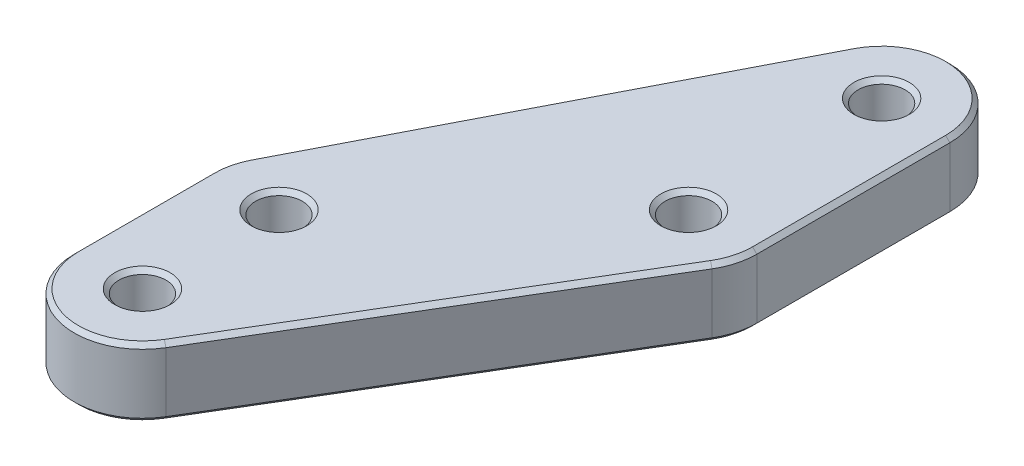
SolidWorks part; units mm, degrees
ref_plane "Front Plane" through (0, 0, 0) normal (0, 0, 1) x (1, 0, 0)
ref_plane "Top Plane" through (0, 0, 0) normal (0, 1, 0) x (1, 0, 0)
ref_plane "Right Plane" through (0, 0, 0) normal (1, 0, 0) x (0, 0, -1)
sketch "Sketch1" plane through (0, 0, 0) normal (0, 1, 0) x (1, 0, 0)
  line L0 (-25.4, -19.05) -> (-25.4, -31.75)
  line L1 (5.4451, -3.267) -> (-13.6049, -35.017)
  line L2 (-24.6959, -16.1437) -> (-5.6459, 20.8641)
  line L3 (6.35, 17.9578) -> (6.35, 0)
  circle A0 centre (0, 0) radius 2.1828
  circle A1 centre (0, 17.9578) radius 2.1828
  circle A2 centre (-19.05, -19.05) radius 2.1828
  circle A3 centre (-19.05, -31.75) radius 2.1828
  arc A4 (-25.4, -31.75) -> (-13.6049, -35.017) centre (-19.05, -31.75) ccw
  arc A5 (-24.6959, -16.1437) -> (-25.4, -19.05) centre (-19.05, -19.05) ccw
  arc A6 (5.4451, -3.267) -> (6.35, 0) centre (0, 0) ccw
  arc A7 (6.35, 17.9578) -> (-5.6459, 20.8641) centre (0, 17.9578) ccw
  dimension "D2" = 4.3656
  dimension "D3" = 4.3656
  dimension "D6" = 4.3656
  dimension "D8" = 4.3656
  dimension "D9" = 12.7
  dimension "D10" = 12.7
  dimension "D11" = 12.7
  dimension "D12" = 12.7
  dimension "D1" = 17.9578
  dimension "D4" = 19.05
  dimension "D5" = 19.05
  dimension "D7" = 12.7
  dimension "D13" = 17.9578
extrude "Boss-Extrude1" add sketch "Sketch1" along normal mid plane 6.35
chamfer "Chamfer1" distance 0.3969 angle 45 24 edges at (-19.05, -3.175, 33.9328) (-19.05, -3.175, 21.2328) (0, -3.175, -15.775) (0, -3.175, 2.1828) (-25.4, -3.175, 25.4) (-20.745, -3.175, 37.8696) (-4.0799, -3.175, 19.142) (6.1196, -3.175, 1.695) (6.35, -3.175, -8.9789) (1.4952, -3.175, -24.1293) (-15.1709, -3.175, -2.3602) (-25.2215, -3.175, 17.5548) (-19.05, 3.175, 33.9328) (0, 3.175, -15.775) (-15.1709, 3.175, -2.3602) (1.4952, 3.175, -24.1293) (6.35, 3.175, -8.9789) (6.1196, 3.175, 1.695) (-4.0799, 3.175, 19.142) (-20.745, 3.175, 37.8696) (-25.4, 3.175, 25.4) (-25.2215, 3.175, 17.5548) (0, 3.175, 2.1828) (-19.05, 3.175, 21.2328)
